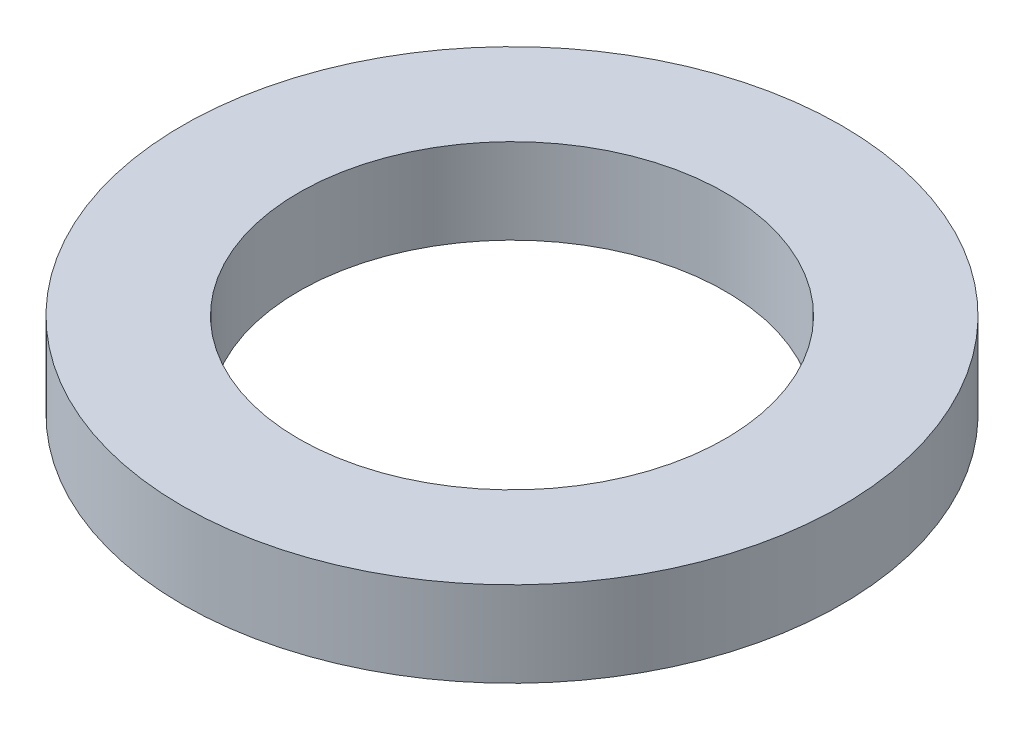
SolidWorks part; units mm, degrees
ref_plane "Front Plane" through (0, 0, 0) normal (0, 0, 1) x (1, 0, 0)
ref_plane "Top Plane" through (0, 0, 0) normal (0, 1, 0) x (1, 0, 0)
ref_plane "Right Plane" through (0, 0, 0) normal (1, 0, 0) x (0, 0, -1)
sketch "Sketch1" plane through (0, 0, 0) normal (0, 1, 0) x (1, 0, 0)
  circle A0 centre (0, 0) radius 42.5
  dimension "FLANGE_OD" = 85
extrude "Boss-Extrude1" add sketch "Sketch1" along normal blind 11
sketch "Sketch2" plane through (0, 0, 0) normal (0, 1, 0) x (1, 0, 0)
  circle A0 centre (0, 0) radius 27.5
  dimension "BORE_D" = 55
extrude "Cut-Extrude1" cut sketch "Sketch2" along normal through all
sketch "Sketch3" plane through (0, 11, 0) normal (0, 1, 0) x (1, 0, 0)
  circle A0 centre (0, 0) radius 18.0028 construction
  circle A1 centre (-18.0028, 0) radius 2.5053
  dimension "BOLT_D" = 5.0107
  dimension "BOLT_PCD" = 36.0056
extrude "Cut-Extrude2" cut sketch "Sketch3" against normal blind 8.3011 rebuild error yes
pattern_circular "CirPattern1" count 5 over 360 rebuild error yes
